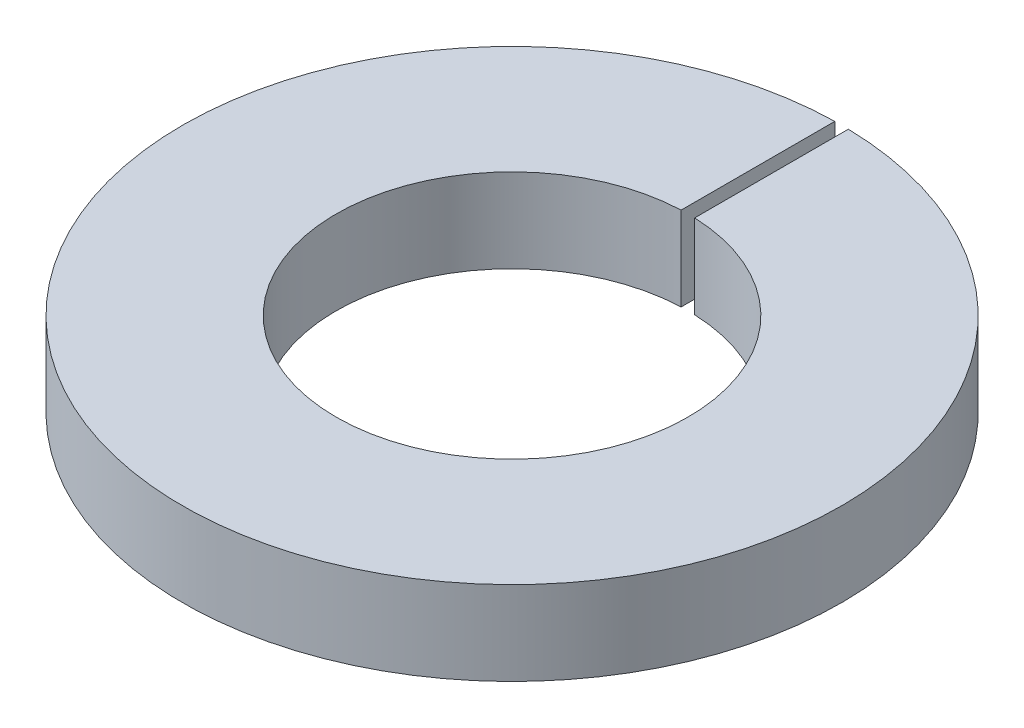
SolidWorks part; units mm, degrees
material "Plain Carbon Steel"
ref_plane "Front Plane" through (0, 0, 0) normal (0, 0, 1) x (1, 0, 0)
ref_plane "Top Plane" through (0, 0, 0) normal (0, 1, 0) x (1, 0, 0)
ref_plane "Right Plane" through (0, 0, 0) normal (1, 0, 0) x (0, 0, -1)
sketch "Sketch1" plane through (0, 0, 0) normal (0, 0, 1) x (1, 0, 0)
  circle A0 centre (0, 0) radius 3.302
  circle A1 centre (0, 0) radius 6.1849
  dimension "OD" = 12.3698
  dimension "ID" = 6.604
sketch "Sketch2" plane through (0, 0, 0) normal (1, 0, 0) x (0, 0, -1)
  line L0 (0, 0) -> (0, 6.1849) construction
  line L1 (0, 6.1849) -> (0, -6.1849) construction
  line L4 (0.1575, 6.1849) -> (1.7323, 6.1849)
  line L5 (1.7323, 6.1849) -> (1.7323, 3.302)
  line L6 (1.7323, 3.302) -> (0.1575, 3.302)
  line L7 (0.1575, 3.302) -> (0.1575, 6.1849)
  point P6 (0, 3.302)
  point P14 (0, -6.1849)
  dimension "Thickness" = 1.5748
  dimension "D1" = 0.1575
ref_plane "Plane1" through (0, 0, -1.7323) normal (0, 0, 1) x (1, 0, 0)
sketch "Sketch3" plane through (0, 0, -1.7323) normal (0, 0, 1) x (1, 0, 0)
  circle A0 centre (0, 0) radius 6.1849 construction
  circle A1 centre (0, 0) radius 6.1849
curve "Helix/Spiral1" pitch 1.7323 height 1.7323 turns 1
sketch "Sketch4" plane through (0, 0, 0) normal (1, 0, 0) x (0, 0, -1)
  line L0 (0.1575, 3.302) -> (0.1575, 6.1849) construction
  line L1 (1.7323, 3.302) -> (0.1575, 3.302) construction
  line L2 (1.7323, 6.1849) -> (1.7323, 3.302) construction
  line L3 (0.1575, 6.1849) -> (1.7323, 6.1849) construction
  line L4 (0.1575, 3.302) -> (0.1575, 6.1849)
  line L5 (1.7323, 3.302) -> (0.1575, 3.302)
  line L6 (1.7323, 6.1849) -> (1.7323, 3.302)
  line L7 (0.1575, 6.1849) -> (1.7323, 6.1849)
sweep "Sweep1" [suppressed] add profiles "Sketch4" path "Helix/Spiral1"
fillet "Fillet1" [suppressed] radius 0.0787
sketch "Sketch5" plane through (0, 0, 0) normal (0, 1, 0) x (1, 0, 0)
  line L2 (-0.127, 6.1836) -> (-0.127, 3.2996)
  line L4 (0.127, 6.1836) -> (0.127, 3.2996)
  arc A0 (-0.127, 6.1836) -> (0.127, 6.1836) centre (0, 0) ccw
  arc A1 (-0.127, 3.2996) -> (0.127, 3.2996) centre (0, 0) ccw
  dimension "D1" = 6.604
  dimension "D2" = 12.3698
extrude "Boss-Extrude1" add sketch "Sketch5" along normal blind 1.5748
equation "\"D1@Sketch2\"=\"Thickness@Sketch2\"*0.1"
equation "\"D4@Helix/Spiral1\"=\"Thickness@Sketch2\"+\"D1@Sketch2\""
equation "\"D1@Fillet1\"=\"D1@Sketch2\"*0.5"
